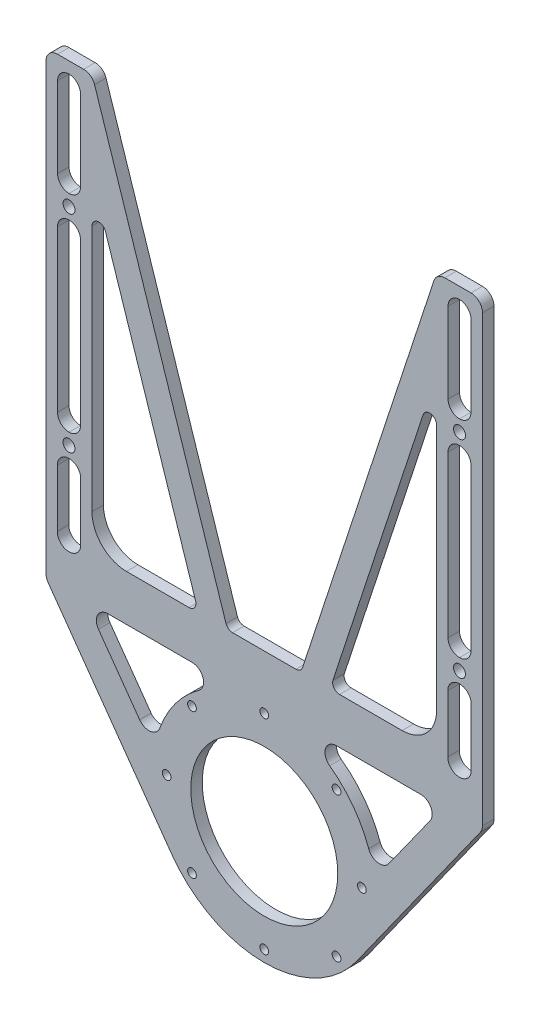
SolidWorks part; units mm, degrees
material "Thornel Mat VMA"
ref_plane "前视基准面" through (0, 0, 0) normal (0, 0, 1) x (1, 0, 0)
ref_plane "上视基准面" through (0, 0, 0) normal (0, 1, 0) x (1, 0, 0)
ref_plane "右视基准面" through (0, 0, 0) normal (1, 0, 0) x (0, 0, -1)
other "Configuration Table"
sketch "草图1" plane through (0, 0, 0) normal (0, 0, 1) x (1, 0, 0)
  line L0 (-95, 0) -> (95, 0) construction
  line L1 (0, 0) -> (0, -48) construction
  line L2 (-95, 0) -> (-75, 0)
  line L3 (-95, 0) -> (-95, 200)
  line L4 (-95, 200) -> (-75, 200)
  line L5 (-75, 0) -> (-75, 200)
  line L6 (95, 0) -> (75, 0)
  line L7 (95, 0) -> (95, 200)
  line L8 (95, 200) -> (75, 200)
  line L9 (75, 0) -> (75, 200)
  line L10 (-95, 0) -> (95, 0)
  line L11 (-95, 0) -> (-95, -83)
  line L12 (-95, -83) -> (95, -83)
  line L13 (95, 0) -> (95, -83)
  circle A0 centre (0, -48) radius 28.5
  point P4 (0, 0)
  dimension "D5" = 48
  dimension "D6" = 57
  dimension "D4" = 35
  dimension "D1" = 20
  dimension "D2" = 200
  dimension "D3" = 150
extrude "凸台-拉伸1" add sketch "草图1" along normal mid plane 5 contours L2 L5 L4 L3 | L13 L6 L10 L2 L11 L12 A0 | L9 L6 L7 L8
sketch "草图2" plane through (0, 0, 2.5) normal (0, 0, 1) x (1, 0, 0)
  line L0 (-48.6858, 0) -> (49951.3142, 0) construction
  line L2 (75, 0) -> (-75, 0) construction
  line L3 (-95, 0) -> (-25.6606, -72.5313)
  line L4 (-95, -83) -> (-95, 200) construction
  line L5 (25.6606, -72.5313) -> (95, 0)
  line L6 (-95, 0) -> (95, 0)
  line L7 (95, 200) -> (95, -83) construction
  line L16 (-95, 200) -> (-95, -83)
  line L17 (-95, -83) -> (95, -83)
  line L18 (95, -83) -> (95, 200)
  line L19 (95, 200) -> (75, 200)
  line L20 (75, 200) -> (75, 0)
  line L21 (75, 0) -> (-75, 0)
  line L22 (-75, 0) -> (-75, 200)
  line L23 (-75, 200) -> (-95, 200)
  line L24 (-95, 200) -> (-95, -83)
  line L25 (-95, -83) -> (95, -83)
  line L26 (95, -83) -> (95, 200)
  line L27 (95, 200) -> (75, 200)
  line L28 (75, 200) -> (75, 0)
  line L29 (75, 0) -> (-75, 0)
  line L30 (-75, 0) -> (-75, 200)
  line L31 (-75, 200) -> (-95, 200)
  circle A0 centre (0, -48) radius 35.5
  circle A1 centre (0, -48) radius 28.5 construction
  line M1 (-95, 200) -> (-95, -83)
  line M2 (-95, -83) -> (95, -83)
  line M3 (95, -83) -> (95, 200)
  dimension "D1" = 7
  dimension "D2" = 0
extrude "切除-拉伸2" cut sketch "草图2" against normal blind 10 contours A0 L3 M1 M2 | A0 L25 L5 M3
sketch "草图3" plane through (0, 0, 2.5) normal (0, 0, 1) x (1, 0, 0)
  line L0 (-95, 0) -> (-40.3087, -76.7308)
  line L1 (95, 0) -> (40.3087, -76.7308)
  line L2 (-95, 0) -> (95, 0)
  circle A0 centre (0, -48) radius 49.5
  circle A1 centre (0, -48) radius 28.5 construction
  circle A2 centre (0, -48) radius 28.5
  circle M1 centre (0, -48) radius 28.5
  line M2 (-95, 0) -> (-25.6606, -72.5313)
  arc M3 (-25.6606, -72.5313) -> (-5.9372, -83) centre (0, -48) ccw
  line M4 (-5.9372, -83) -> (5.9372, -83)
  arc M5 (5.9372, -83) -> (25.6606, -72.5313) centre (0, -48) ccw
  line M6 (25.6606, -72.5313) -> (95, 0)
  line M10 (75, 0) -> (-75, 0)
  dimension "D1" = 99
extrude "凸台-拉伸2" add sketch "草图3" against normal up to surface (5 mm away) contours A0 L2 M6 M10 M2 | A0 M6 M2 M3 M4 M5 M1 | A0 L0 M2 | A0 L1 M6 | A0 M2 M6 M5 M4 M3
sketch "草图4" plane through (0, 0, 2.5) normal (0, 0, 1) x (1, 0, 0)
  line L0 (85, 200) -> (85, 0) construction
  line L1 (95, 200) -> (75, 200) construction
  line L2 (85, 0) -> (95, 0) construction
  line L3 (95, 200) -> (95, 0) construction
  line L4 (85, 145) -> (85, 55) construction
  circle A0 centre (85, 145) radius 2.6
  circle A1 centre (85, 55) radius 2.6
  point P11 (85, 100)
  dimension "D2" = 5.2
  dimension "D1" = 90
extrude "切除-拉伸3" cut sketch "草图4" against normal blind 10
mirror "镜向1" about plane through (0, 0, 0) normal (1, 0, 0) of "切除-拉伸3"
sketch "草图5" plane through (0, 0, 2.5) normal (0, 0, 1) x (1, 0, 0)
  line L0 (75, 0) -> (75, 200) construction
  line L1 (-75, 0) -> (75, 0)
  line L2 (-75, 0) -> (-75, 20)
  line L3 (-75, 20) -> (75, 20)
  line L4 (75, 0) -> (75, 20)
  line L5 (-75, 0) -> (-75, 200) construction
  dimension "D1" = 20
extrude "凸台-拉伸3" add sketch "草图5" against normal up to surface (5 mm away)
fillet "圆角1" radius 15 2 edges at (75, 20, 0) (-75, 20, 0)
sketch "草图6" plane through (0, 0, 2.5) normal (0, 0, 1) x (1, 0, 0)
  line L0 (-85, 200) -> (-85, -49800) construction
  line L9 (-95, 200) -> (-75, 200) construction
  line L10 (85, 200) -> (85, -49800) construction
  line L11 (95, 200) -> (75, 200) construction
  line L12 (-75, 35) -> (-75, 200) construction
  line L13 (-90, 150) -> (-80, 150)
  line L14 (-90, 150) -> (-90, 195)
  line L15 (-90, 195) -> (-80, 195)
  line L16 (-80, 150) -> (-80, 195)
  line L17 (-90, 150) -> (-80, 195) construction
  line L18 (-90, 195) -> (-80, 150) construction
  line L19 (-90, 140) -> (-80, 140)
  line L20 (-90, 140) -> (-90, 60)
  line L21 (-90, 60) -> (-80, 60)
  line L22 (-80, 140) -> (-80, 60)
  line L23 (-90, 140) -> (-80, 60) construction
  line L24 (-90, 60) -> (-80, 140) construction
  line L26 (60, 20) -> (-60, 20) construction
  line L33 (0, 20) -> (0, -16) construction
  line L35 (90, 195) -> (80, 195)
  line L36 (80, 150) -> (80, 195)
  line L37 (90, 150) -> (80, 150)
  line L38 (90, 150) -> (90, 195)
  line L39 (90, 60) -> (80, 60)
  line L40 (80, 140) -> (80, 60)
  line L41 (90, 140) -> (80, 140)
  line L42 (90, 140) -> (90, 60)
  circle A0 centre (-85, 145) radius 2.6 construction
  circle A1 centre (-85, 55) radius 2.6 construction
  circle A2 centre (0, -48) radius 32
  point P4 (-85, 200)
  point P9 (85, 200)
  point P10 (-85, 172.5)
  point P15 (-85, 100)
  circle M25 centre (0, -48) radius 28.5
  dimension "D1" = 5
  dimension "D2" = 5
  dimension "D6" = 64
  dimension "D3" = 5
  dimension "D4" = 5
  dimension "D5" = 5
extrude "切除-拉伸4" cut sketch "草图6" against normal blind 10 contours L13 L16 L15 L14 | L22 L19 L20 L21 | L42 L41 L40 L39 | L37 L38 L35 L36 | A2 M25
sketch "草图7" plane through (0, 0, 2.5) normal (0, 0, 1) x (1, 0, 0)
  line L0 (-71.9305, 10) -> (49928.0695, 10) construction
  line L3 (-85, 55) -> (-85, 10) construction
  line L4 (85, 55) -> (85, 10) construction
  line L5 (-85, 45) -> (-85, 20) construction
  line L6 (-79.8923, 45) -> (-79.8923, 20)
  line L7 (-90.1077, 45) -> (-90.1077, 20)
  line L8 (85, 45) -> (85, 20) construction
  line L9 (90.1077, 45) -> (90.1077, 20)
  line L10 (79.8923, 45) -> (79.8923, 20)
  line L11 (-85, 32.5) -> (85, 32.5) construction
  line L12 (-85, 51) -> (-85, 14) construction
  line L13 (-95, 0) -> (-95, 200) construction
  arc A0 (-79.8923, 45) -> (-90.1077, 45) centre (-85, 45) ccw
  arc A1 (-90.1077, 20) -> (-79.8923, 20) centre (-85, 20) ccw
  arc A2 (90.1077, 45) -> (79.8923, 45) centre (85, 45) ccw
  arc A3 (79.8923, 20) -> (90.1077, 20) centre (85, 20) ccw
  circle A5 centre (-85, 55) radius 2.6 construction
  point P12 (-85, 32.5)
  point P18 (85, 32.5)
  point P28 (-85, 32.5)
  point P35 (-85, 32.5)
  dimension "D1" = 10
  dimension "D2" = 4
  dimension "D4" = 5.1077
  dimension "D5" = 10
  dimension "D3" = 4
  dimension "D6" = 10
extrude "切除-拉伸5" cut sketch "草图7" against normal blind 10
sketch "草图8" plane through (0, 0, 2.5) normal (0, 0, 1) x (1, 0, 0)
  line L0 (-42.5, -48) -> (42.5, -48) construction
  circle A0 centre (0, -48) radius 44.5 construction
  circle A1 centre (0, -3.5) radius 1.9
  circle A2 centre (31.4663, -16.5337) radius 1.9
  circle A4 centre (31.4663, -79.4663) radius 1.9
  circle A5 centre (0, -92.5) radius 1.9
  circle A6 centre (-31.4663, -79.4663) radius 1.9
  circle A8 centre (-31.4663, -16.5337) radius 1.9
  circle A9 centre (44.5, -48) radius 1.9 [skipped]
  circle A10 centre (-44.5, -48) radius 1.9 [skipped]
  circle A11 centre (-42.5, -48) radius 1.9
  circle A12 centre (42.5, -48) radius 1.9
  point P6 (0, -48)
  point P25 (0, -48)
  dimension "D1" = 89
  dimension "D3" = 3.8
  dimension "D2" = 85
  dimension "D4" = 8
extrude "切除-拉伸6" cut sketch "草图8" against normal blind 10
sketch "草图9" plane through (0, 0, 2.5) normal (0, 0, 1) x (1, 0, 0)
  line L0 (-75, 200) -> (5.7014, -46.1306)
  line L1 (-75, 161.4842) -> (-5.7014, -49.8694)
  line L2 (-75, 200) -> (-75, 161.4842)
  line L3 (-75, 35) -> (-75, 200) construction
  line L4 (-86.4027, 196.2613) -> (-5.7014, -49.8694) construction
  line L5 (-28.6101, 20) -> (-15.9816, 20)
  line L6 (60, 20) -> (-60, 20) construction
  circle A0 centre (0, -48) radius 6
  line M25 (60, 20) -> (-60, 20)
  line M27 (-75, 35) -> (-75, 200)
  dimension "D1" = 12
  dimension "D2" = 12
extrude "凸台-拉伸4" add sketch "草图9" against normal up to surface (5 mm away) contours L1 L0 M27 M25
mirror "镜向2" about plane through (0, 0, 0) normal (1, 0, 0) of "凸台-拉伸4"
fillet "圆角3" radius 3 6 edges at (75, 161.4842, 0) (28.6101, 20, 0) (-75, 161.4842, 0) (-28.6101, 20, 0) (15.9816, 20, 0) (-15.9816, 20, 0)
sketch "草图11" plane through (0, 0, 2.5) normal (0, 0, 1) x (1, 0, 0)
  line L0 (-47.8832, -41.9835) -> (-77.8077, 0)
  line L1 (-77.8077, 0) -> (-5, 0)
  line L2 (0, 0.2235) -> (0, -49999.7765) construction
  line L3 (-32.7509, 20) -> (-60, 20) construction
  line L4 (-95, 0) -> (-40.3087, -76.7308) construction
  line L5 (77.8077, 0) -> (5, 0)
  line L6 (47.8832, -41.9835) -> (77.8077, 0)
  circle A0 centre (0, -48) radius 48.2597
  circle A1 centre (0, -48) radius 44.5 construction
  dimension "D1" = 14
  dimension "D3" = 10
  dimension "D2" = 20
extrude "切除-拉伸9" cut sketch "草图11" against normal blind 14 contours A0 L1 L0 | A0 L6 L5
fillet "圆角4" radius 5 22 edges at (-47.8832, -41.9835, 0) (-5, 0, 0) (-80, 60, 0) (-90, 60, 0) (-90, 140, 0) (-80, 140, 0) (80, 150, 0) (80, 195, 0) (90, 195, 0) (90, 150, 0) (-90, 195, 0) (-80, 195, 0) (-80, 150, 0) (-90, 150, 0) (90, 60, 0) (80, 60, 0) (80, 140, 0) (90, 140, 0) (5, 0, 0) (77.8077, 0, 0) (47.8832, -41.9835, 0) (-77.8077, 0, 0)
fillet "圆角5" radius 5 6 edges at (-75, 200, 0) (-95, 200, 0) (95, 0, 0) (95, 200, 0) (75, 200, 0) (-95, 0, 0)
